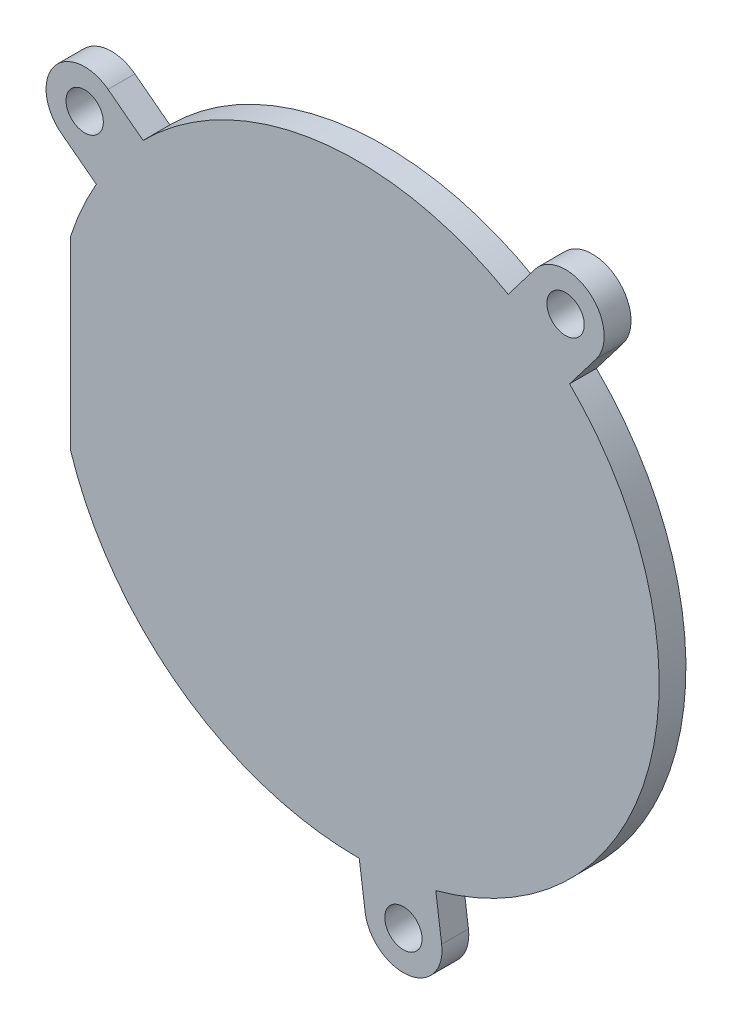
SolidWorks part; units mm, degrees
ref_plane "Front Plane" through (0, 0, 0) normal (0, 0, 1) x (1, 0, 0)
ref_plane "Top Plane" through (0, 0, 0) normal (0, 1, 0) x (1, 0, 0)
ref_plane "Right Plane" through (0, 0, 0) normal (1, 0, 0) x (0, 0, -1)
sketch "Sketch1" plane through (0, 0, 0) normal (0, 0, 1) x (1, 0, 0)
  line L7 (-16.9841, -5.5245) -> (-16.9841, 5.5245)
  line L8 (0.1008, -17.8597) -> (0.449, -20.4433)
  line L9 (4.9801, -19.8325) -> (4.6318, -17.2489)
  line L10 (14.138, 14.7731) -> (12.5574, 12.7)
  line L11 (8.9216, 15.472) -> (10.5023, 17.5451)
  line L12 (-12.7, 12.5574) -> (-14.7731, 14.138)
  line L13 (-17.5451, 10.5023) -> (-15.472, 8.9216)
  arc A7 (-15.472, 8.9216) -> (-16.9841, 5.5245) centre (0, 0) ccw
  arc A8 (-16.9841, -5.5245) -> (0.1008, -17.8597) centre (0, 0) ccw
  arc A9 (0.449, -20.4433) -> (4.9801, -19.8325) centre (2.7145, -20.1379) ccw
  arc A10 (4.6318, -17.2489) -> (12.5574, 12.7) centre (0, 0) ccw
  arc A11 (14.138, 14.7731) -> (10.5023, 17.5451) centre (12.3201, 16.1591) ccw
  arc A12 (8.9216, 15.472) -> (-12.7, 12.5574) centre (0, 0) ccw
  arc A13 (-14.7731, 14.138) -> (-17.5451, 10.5023) centre (-16.1591, 12.3201) ccw
  circle A16 centre (2.7145, -20.1379) radius 1.1049 construction
  circle A17 centre (-16.1591, 12.3201) radius 1.1049
  circle A18 centre (12.3201, 16.1591) radius 1.1049
  circle A19 centre (2.7145, -20.1379) radius 1.1049
  circle A20 centre (-16.1591, 12.3201) radius 1.1049 construction
  circle A21 centre (12.3201, 16.1591) radius 1.1049 construction
  arc A22 (-14.7731, 14.138) -> (-17.5451, 10.5023) centre (-16.1591, 12.3201) ccw construction
extrude "Boss-Extrude1" add sketch "Sketch1" along normal blind 1.5875
